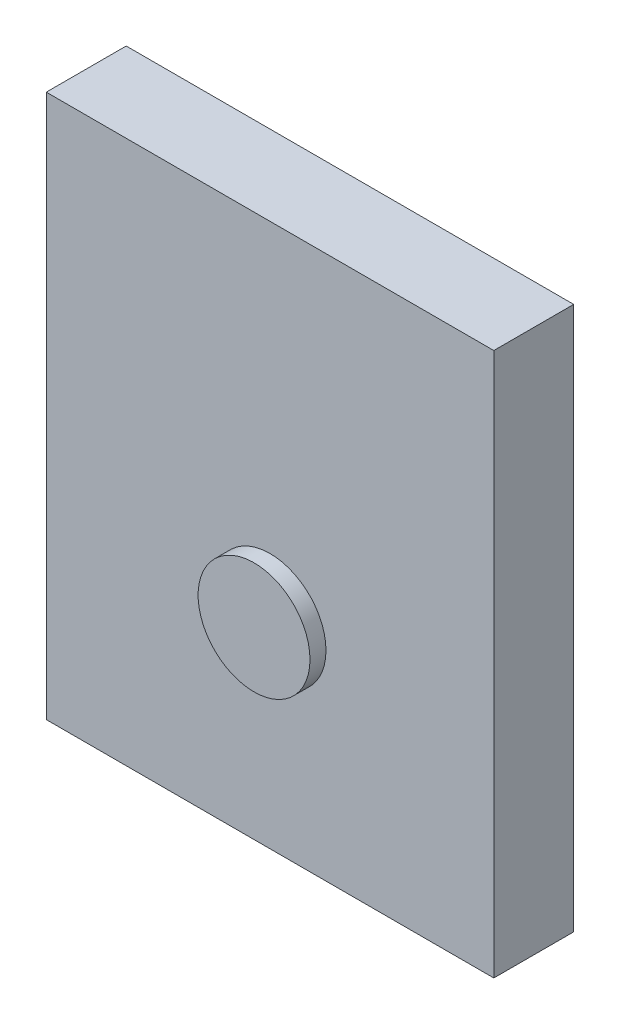
SolidWorks part; units mm, degrees
ref_plane "前视基准面" through (0, 0, 0) normal (0, 0, 1) x (1, 0, 0)
ref_plane "上视基准面" through (0, 0, 0) normal (0, 1, 0) x (1, 0, 0)
ref_plane "右视基准面" through (0, 0, 0) normal (1, 0, 0) x (0, 0, -1)
other "Configuration Table"
sketch "草图1" plane through (0, 0, 0) normal (0, 0, 1) x (1, 0, 0)
  line L1 (8.502, 26.3979) -> (64.502, 26.3979)
  line L2 (8.502, 26.3979) -> (8.502, -41.6021)
  line L3 (8.502, -41.6021) -> (64.502, -41.6021)
  line L4 (64.502, 26.3979) -> (64.502, -41.6021)
  dimension "D1" = 56
  dimension "D2" = 68
extrude "凸台-拉伸1" add sketch "草图1" along normal blind 10
sketch "草图2" plane through (0, 0, 10) normal (0, 0, 1) x (1, 0, 0)
  line L0 (8.502, -41.6021) -> (64.502, -41.6021) construction
  circle A0 centre (36.502, -16.6021) radius 7
  point P5 (36.502, -41.6021)
  dimension "D1" = 14
  dimension "D2" = 25
extrude "凸台-拉伸2" add sketch "草图2" along normal blind 2
